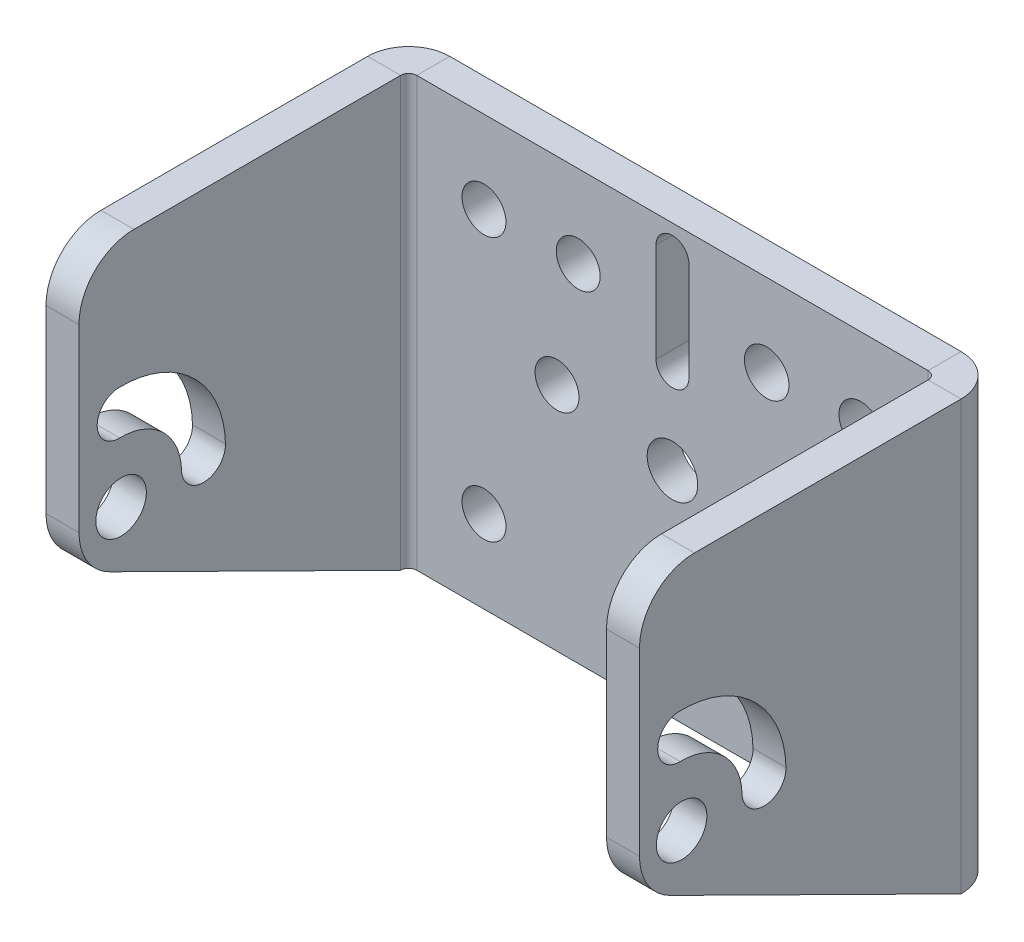
SolidWorks part; units mm, degrees
note: The reader was unsure of these and kept them because the rebuilt part matched: flange length of "Aresta-Flange1".
ref_plane "Plano frontal" through (0, 0, 0) normal (0, 0, 1) x (1, 0, 0)
ref_plane "Plano superior" through (0, 0, 0) normal (0, 1, 0) x (1, 0, 0)
ref_plane "Plano direito" through (0, 0, 0) normal (1, 0, 0) x (0, 0, -1)
sketch "Esboço1" plane through (0, 0, 0) normal (0, 0, 1) x (1, 0, 0)
  line L1 (-21.0063, 15.0091) -> (26.9937, 15.0091)
  line L2 (-21.0063, 15.0091) -> (-21.0063, -23.9909)
  line L3 (-21.0063, -23.9909) -> (26.9937, -23.9909)
  line L4 (26.9937, 15.0091) -> (26.9937, -23.9909)
  dimension "D1" = 48
  dimension "D2" = 39
base flange "Flange-base1" sketch "Esboço1" thickness 3 reverse thickness direction no parameters "D1"=0.7366
sketch "Esboço6" plane through (0, 0, 0) normal (0, 0, 1) x (1, 0, 0)
  line L1 (-14.1563, 7.5091) -> (20.1437, 7.5091)
  line L2 (-14.1563, 7.5091) -> (-14.1563, -16.4909)
  line L3 (-14.1563, -16.4909) -> (20.1437, -16.4909)
  line L4 (20.1437, 7.5091) -> (20.1437, -16.4909)
  line L6 (26.9937, 15.0091) -> (-21.0063, 15.0091) construction
  line L7 (-21.0063, -23.9909) -> (26.9937, -23.9909) construction
  line L8 (2.9937, 15.0091) -> (2.9937, -23.9909) construction
  line L9 (2.9937, 3.5238) -> (2.9937, 12.5238) construction
  line L10 (1.4937, 3.5238) -> (1.4937, 12.5238)
  line L11 (4.4937, 3.5238) -> (4.4937, 12.5238)
  line L12 (-21.0063, -4.4909) -> (26.9937, -4.4909) construction
  line L13 (-21.0063, 15.0091) -> (-21.0063, -23.9909) construction
  line L14 (26.9937, -23.9909) -> (26.9937, 15.0091) construction
  line L15 (2.9937, -12.5057) -> (2.9937, -21.5057) construction
  line L16 (1.4937, -12.5057) -> (1.4937, -21.5057)
  line L17 (4.4937, -12.5057) -> (4.4937, -21.5057)
  circle A0 centre (-14.1563, 7.5091) radius 2
  circle A1 centre (-14.1563, -16.4909) radius 2
  circle A2 centre (20.1437, -16.4909) radius 2
  circle A3 centre (20.1437, 7.5091) radius 2
  circle A4 centre (2.9937, -4.4909) radius 2.3
  arc A5 (1.4937, 3.5238) -> (4.4937, 3.5238) centre (2.9937, 3.5238) ccw
  arc A6 (4.4937, 12.5238) -> (1.4937, 12.5238) centre (2.9937, 12.5238) ccw
  arc A7 (1.4937, -12.5057) -> (4.4937, -12.5057) centre (2.9937, -12.5057) cw
  arc A8 (4.4937, -21.5057) -> (1.4937, -21.5057) centre (2.9937, -21.5057) cw
  point P18 (2.9937, 8.0238)
  point P31 (2.9937, -17.0057)
  dimension "D1" = 6.85
  dimension "D3" = 7.5
  dimension "D4" = 7.5
extrude "Corte-extrusão1" cut sketch "Esboço6" against normal blind 10 contours L1 A0 L2 | L2 A0 L1 | L2 A1 L3 | L3 A1 L2 | A4 | L10 A5 L11 L1 | L11 A6 L10 L1 | A7 L16 L3 L17 | A8 L17 L3 L16 | A2 L3 L4 | A2 L4 L3 | A3 L4 L1 | A3 L1 L4 normal cut yes
edge flange "Aresta-Flange1" sketch "Esboço11" flange profiles "Esboço11", "Esboço12" flange angle 90 flange length 33 flange position material outside bend radius 0.7366 thickness 3 parameters "D6"=10, "D8"=1
sketch "Esboço11" plane through (26.9937, 0, 0) normal (1, 0, 0) x (0, 1, 0)
  line L0 (-23.9909, 0) -> (15.0091, 0) construction
  line L1 (-23.9909, 0) -> (15.0091, 0)
  line L2 (-23.9909, 0) -> (-23.9909, 30)
  line L3 (-23.9909, 30) -> (15.0091, 30)
  line L4 (15.0091, 30) -> (15.0091, 0)
  dimension "D1" = 30
sketch "Esboço12" plane through (-21.0063, 0, 0) normal (-1, 0, 0) x (0, -1, 0)
  line L0 (-15.0091, 0) -> (23.9909, 0) construction
  line L1 (-15.0091, 0) -> (23.9909, 0)
  line L2 (-15.0091, 0) -> (-15.0091, 30)
  line L3 (-15.0091, 30) -> (23.9909, 30)
  line L4 (23.9909, 30) -> (23.9909, 0)
bend "DobradeAresta1" bend radius 0.7366 bend angle 90 parameters "D5"=1
bend "DobradeAresta2" bend radius 0.7366 bend angle 90 parameters "D5"=2
sketch "Esboço13" plane through (-24.0063, 0, 0) normal (-1, 0, 0) x (0, 0, 1)
  line L0 (0.7366, -23.9909) -> (30, -9.4909) construction
  line L1 (30, -23.9909) -> (30, 15.0091) construction
  line L2 (30, -9.4909) -> (0.7366, 15.0091) construction
  line L3 (0.7366, -23.9909) -> (30, -23.9909)
  line L4 (30, -23.9909) -> (30, -9.4909)
  line L5 (30, -9.4909) -> (0.7366, -23.9909)
  circle A0 centre (26.1662, -6.2812) radius 2.3
  arc A1 (26.3439, 1.2167) -> (18.6683, -6.1036) centre (26.1662, -6.2812) ccw construction
  arc A6 (26.3912, 3.2161) -> (16.6689, -6.0562) centre (26.1662, -6.2812) ccw
  arc A7 (26.2965, -0.7828) -> (20.6678, -6.151) centre (26.1662, -6.2812) ccw
  arc A8 (26.2965, -0.7828) -> (26.3912, 3.2161) centre (26.3439, 1.2167) ccw
  arc A9 (16.6689, -6.0562) -> (20.6678, -6.151) centre (18.6683, -6.1036) ccw
  point P12 (20.99, -0.8538)
  dimension "D3" = 4.6
  dimension "D4" = 3.6561
  dimension "D6" = 4
  dimension "D1" = 14.5
  dimension "D2" = 5
  dimension "D7" = 7.5
extrude "Corte-extrusão2" cut sketch "Esboço13" against normal blind 70 normal cut yes
fillet "Filete1" radius 5 4 edges at (28.4937, -9.4909, 30) (28.4937, 15.0091, 30) (-22.5063, -9.4909, 30) (-22.5063, 15.0091, 30)
sketch "Esboço14" plane through (0, 0, 0) normal (0, 0, 1) x (1, 0, 0)
  line L0 (-14.1563, 7.5091) -> (20.1437, 7.5091) construction
  line L1 (2.9937, 12.5238) -> (2.9937, -4.4909) construction
  line L2 (26.2571, 15.0091) -> (-20.2697, 15.0091) construction
  circle A0 centre (-5.5813, 7.5091) radius 1.9979
  circle A1 centre (11.5687, 7.5091) radius 2.0261
  circle A2 centre (13.4937, -2.9909) radius 2
  circle A3 centre (-7.5063, -2.9909) radius 2
  dimension "D2" = 18
  dimension "D1" = 17.15
  dimension "D3" = 21
extrude "Corte-extrusão4" cut sketch "Esboço14" against normal blind 3 normal cut yes
sketch "Curva-Linhas1" [suppressed] plane through (0, 0, 0) normal (0, 1, 0) x (1, 0, 0)
sketch "Caixa delimitadora1" [suppressed] plane through (0, 0, 0) normal (0, 1, 0) x (1, 0, 0)
sheet metal parameters "Chapa metálica1" thickness 3 parameters "D1"=0.7366
flat pattern "Padrão-Plano1" [suppressed]
sketch "Curva-Linhas2" plane through (0, 0, 0) normal (0, 1, 0) x (1, 0, 0)
sketch3d "Caixa delimitadora2" [suppressed]
  line L0 (21.0063, -23.9909, 0) -> (-26.9937, -23.9909, 0) construction
  line L1 (21.0063, 15.0091, 0) -> (-26.9937, 15.0091, 0) construction
  line L2 (21.0063, -23.9909, 0) -> (21.0063, 15.0091, 0) construction
  line L3 (-26.9937, -23.9909, 0) -> (-26.9937, 15.0091, 0) construction
sheet metal parameters "Chapa metálica2" thickness 3 parameters "D1"=0.7366
flat pattern "Padrão-Plano1"
sketch "Curva-Linhas2" plane through (0, 0, 0) normal (0, 1, 0) x (1, 0, 0)
sketch3d "Caixa delimitadora2" [suppressed]
  line L0 (-21.0063, -23.9909, 0) -> (26.9937, -23.9909, 0) construction
  line L1 (-21.0063, 15.0091, 0) -> (26.9937, 15.0091, 0) construction
  line L2 (-21.0063, -23.9909, 0) -> (-21.0063, 15.0091, 0) construction
  line L3 (26.9937, -23.9909, 0) -> (26.9937, 15.0091, 0) construction
sheet metal parameters "Chapa metálica3" thickness 3 parameters "D1"=0.7366
flat pattern "Padrão-Plano1"
sketch "Curva-Linhas2" plane through (0, 0, 0) normal (0, 0, 1) x (1, 0, 0)
  line L0 (-22.0263, 15.0091) -> (-22.0263, -23.9909) construction
  line L1 (28.0138, -23.9909) -> (28.0138, 15.0091) construction
  line L2 (-22.0263, 15.0091) -> (-22.0263, -23.9909) construction
  line L3 (28.0138, -23.9909) -> (28.0138, 15.0091) construction
sketch3d "Caixa delimitadora2" [suppressed]
  line L0 (-50.0463, -23.9909, 0) -> (56.0338, -23.9909, 0) construction
  line L1 (-50.0463, 15.0091, 0) -> (56.0338, 15.0091, 0) construction
  line L2 (-50.0463, -23.9909, 0) -> (-50.0463, 15.0091, 0) construction
  line L3 (56.0338, -23.9909, 0) -> (56.0338, 15.0091, 0) construction
bend of the flat pattern "Planificar-<DobradeAresta1>1"
bend of the flat pattern "Planificar-<DobradeAresta2>1"
sheet metal parameters "Chapa metálica4" thickness 3 parameters "D1"=0.7366
flat pattern "Padrão-Plano1"
sketch "Curva-Linhas2" plane through (0, 0, 0) normal (0, 0, 1) x (1, 0, 0)
  line L0 (-22.0263, 15.0091) -> (-22.0263, -23.9909) construction
  line L1 (28.0138, -23.9909) -> (28.0138, 15.0091) construction
  line L2 (-22.0263, 15.0091) -> (-22.0263, -23.9909) construction
  line L3 (28.0138, -23.9909) -> (28.0138, 15.0091) construction
sketch3d "Caixa delimitadora2" [suppressed]
  line L0 (-50.0463, -23.9909, 0) -> (56.0338, -23.9909, 0) construction
  line L1 (-50.0463, 15.0091, 0) -> (56.0338, 15.0091, 0) construction
  line L2 (-50.0463, -23.9909, 0) -> (-50.0463, 15.0091, 0) construction
  line L3 (56.0338, -23.9909, 0) -> (56.0338, 15.0091, 0) construction
bend of the flat pattern "Planificar-<DobradeAresta1>1"
bend of the flat pattern "Planificar-<DobradeAresta2>1"
sheet metal parameters "Chapa metálica6" thickness 3 parameters "D1"=0.7366
flat pattern "Padrão-Plano1"
sketch "Curva-Linhas2" plane through (0, 0, 0) normal (0, 0, 1) x (1, 0, 0)
  line L0 (-22.0263, 15.0091) -> (-22.0263, -23.9909) construction
  line L1 (28.0138, -23.9909) -> (28.0138, 15.0091) construction
  line L2 (-22.0263, 15.0091) -> (-22.0263, -23.9909) construction
  line L3 (28.0138, -23.9909) -> (28.0138, 15.0091) construction
sketch3d "Caixa delimitadora2" [suppressed]
  line L0 (-53.0463, -23.9909, 0) -> (59.0338, -23.9909, 0) construction
  line L1 (-53.0463, 15.0091, 0) -> (59.0338, 15.0091, 0) construction
  line L2 (-53.0463, -23.9909, 0) -> (-53.0463, 15.0091, 0) construction
  line L3 (59.0338, -23.9909, 0) -> (59.0338, 15.0091, 0) construction
bend of the flat pattern "Planificar-<DobradeAresta1>1"
bend of the flat pattern "Planificar-<DobradeAresta2>1"
